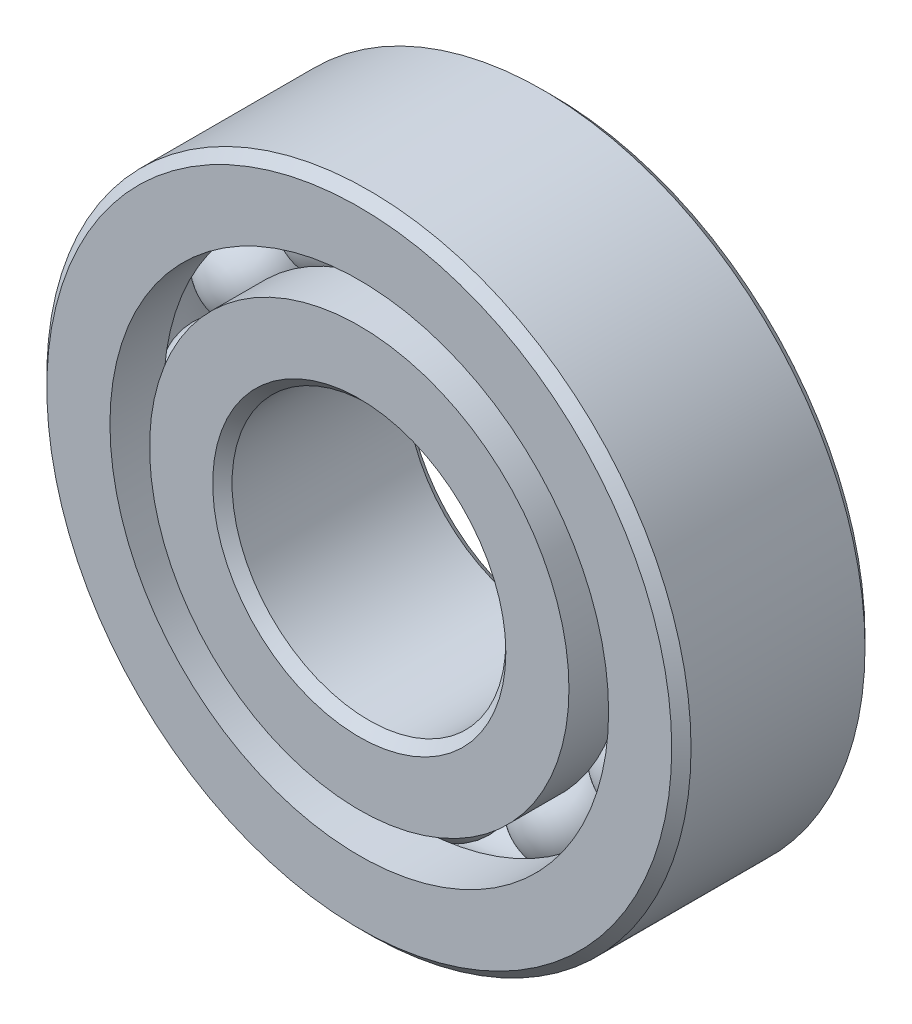
SolidWorks part; units mm, degrees
note: '?' marks a value the reader was unsure of.
ref_plane "Front Plane" through (0, 0, 0) normal (0, 0, 1) x (1, 0, 0)
ref_plane "Top Plane" through (0, 0, 0) normal (0, 1, 0) x (1, 0, 0)
ref_plane "Right Plane" through (0, 0, 0) normal (1, 0, 0) x (0, 0, -1)
sketch "Sketch1" plane through (0, 0, 0) normal (1, 0, 0) x (0, 0, -1)
  line L0 (-6, 0) -> (6, 0) construction
  line L1 (0, 20) -> (0, -20) construction
  line L2 (5.4, 20) -> (-5.4, 20)
  line L3 (-5.4, 20) -> (-6, 19.4)
  line L4 (-6, 19.4) -> (-6, 15.4808)
  line L5 (-6, 15.4808) -> (-2.6667, 15.4808)
  line L6 (6, 15.4808) -> (2.6667, 15.4808)
  line L7 (6, 19.4) -> (6, 15.4808)
  line L8 (5.4, 20) -> (6, 19.4)
  line L9 (0, 20) -> (0, 14.25) construction
  line L10 (0, 14.25) -> (0, 8.5) construction
  arc A0 (-2.6667, 15.4808) -> (2.6667, 15.4808) centre (0, 14.25) cw
  point P14 (0, 8.5)
  dimension "Width" = 12
  dimension "OD" = 40
  dimension "D1" = 45
  dimension "D2" = 0.6
  dimension "Shaft Dia" = 17
  dimension "D3" = 5.3333
  dimension "D4" = 1.2308
revolve "Revolve1" add sketch "Sketch1" angle 360 about L0
sketch "Sketch3" plane through (0, 0, 0) normal (1, 0, 0) x (0, 0, -1)
  line L0 (-6, 13.0192) -> (-2.6667, 13.0192)
  line L1 (0, 20) -> (0, -20) construction
  line L2 (-6, 19.4) -> (-6, 15.4808) construction
  line L3 (-6, 13.0192) -> (-6, 9.1)
  line L4 (-5.4, 20) -> (-6, 19.4) construction
  line L5 (-6, 9.1) -> (-5.4, 8.5)
  line L6 (-5.4, 8.5) -> (5.4, 8.5)
  line L7 (5.4, 20) -> (5.4, -20) construction
  line L8 (5.4, 8.5) -> (6, 9.1)
  line L9 (6, -19.4) -> (6, 19.4) construction
  line L10 (6, 9.1) -> (6, 13.0192)
  line L11 (6, 13.0192) -> (2.6667, 13.0192)
  line L13 (5.4, 20) -> (6, 19.4) construction
  arc A0 (2.6667, 15.4808) -> (-2.6667, 15.4808) centre (0, 14.25) ccw construction
  arc A1 (2.6667, 13.0192) -> (-2.6667, 13.0192) centre (0, 14.25) cw
revolve "Revolve3" add sketch "Sketch3" angle 360 about L0
sketch "Sketch4" plane through (0, 0, 0) normal (1, 0, 0) x (0, 0, -1)
  line L0 (-2.937, 14.25) -> (2.937, 14.25)
  arc A2 (-2.937, 14.25) -> (2.937, 14.25) centre (0, 14.25) cw
  arc A3 (2.6667, 15.4808) -> (-2.6667, 15.4808) centre (0, 14.25) ccw construction
revolve "Revolve4" add sketch "Sketch4" angle 360 about L0
ref_axis "Axis1" through (0, 0, -6) along (0, 0, 1)?
pattern_circular "CirPattern1" count 12 every 30 about axis through (0, 0, 0) along (0, 0, 1) of bodies 104
sketch "Sketch5" plane through (0, 0, 0) normal (1, 0, 0) x (0, 0, -1)
  line L0 (-6, 15.4808) -> (-2.6667, 15.4808) construction
  line L1 (-5.7, 15.4808) -> (-2.937, 15.4808)
  line L2 (-5.7, 15.4808) -> (-5.7, 13.0192)
  line L3 (-5.7, 13.0192) -> (-2.937, 13.0192)
  line L4 (-2.937, 15.4808) -> (-2.937, 13.0192)
  line L5 (-6, 13.0192) -> (-2.6667, 13.0192) construction
  line L6 (6, 15.4808) -> (2.6667, 15.4808) construction
  line L7 (5.7, 15.4808) -> (2.937, 15.4808)
  line L8 (5.7, 15.4808) -> (5.7, 13.0192)
  line L9 (5.7, 13.0192) -> (2.937, 13.0192)
  line L10 (2.937, 15.4808) -> (2.937, 13.0192)
  line L11 (6, 13.0192) -> (2.6667, 13.0192) construction
  line L12 (-5.4, 20) -> (-6, 19.4) construction
  point P18 (-5.7, 19.7)
equation "\"D2@Sketch1\" = \"Width@Sketch1\"*.05"
equation "\"D3@Sketch1\" = \"Width@Sketch1\"/2.25"
equation "\"D4@Sketch1\" = (((\"OD@Sketch1\"-\"Width@Sketch1\")/2)/3.25)/3.5"
equation "\"D2@CirPattern1\" = 360/\"Balls@CirPattern1\""
